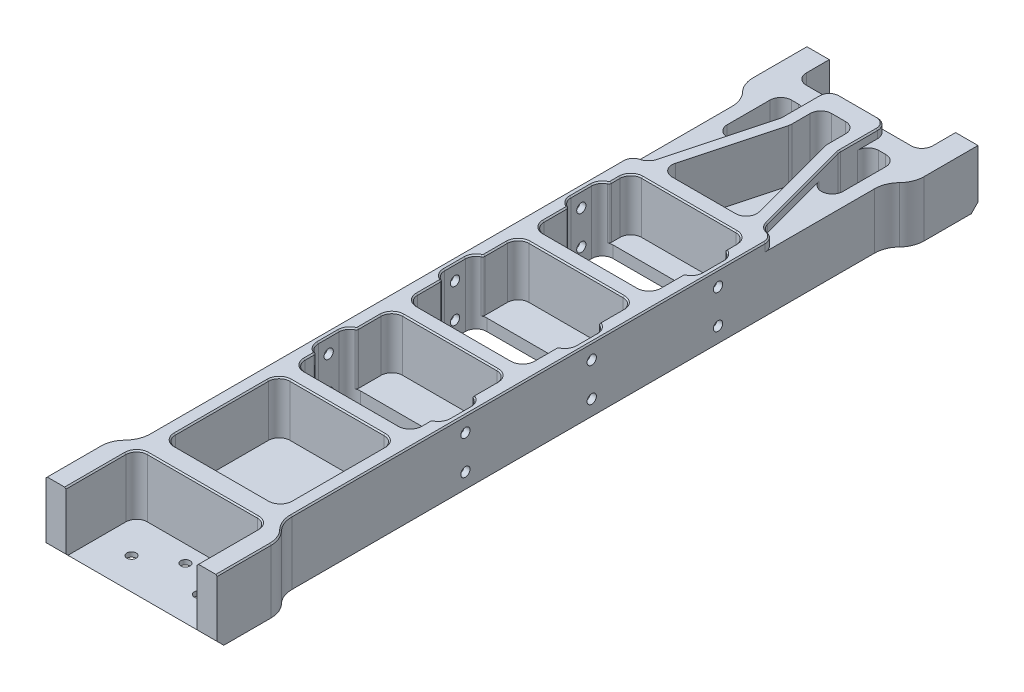
SolidWorks part; units mm, degrees
note: '?' marks a value the reader was unsure of.
material "Delrin 150"
ref_plane "Front Plane" through (0, 0, 0) normal (0, 0, 1) x (1, 0, 0)
ref_plane "Top Plane" through (0, 0, 0) normal (0, 1, 0) x (1, 0, 0)
ref_plane "Right Plane" through (0, 0, 0) normal (1, 0, 0) x (0, 0, -1)
ref_axis "Axis1" through (0, 0, -88.99) along (0, 0, 1)?
ref_axis "Axis2" through (0, -55, 0) along (0, 1, 0)?
ref_axis "Axis3" through (-88.99, 0, 0) along (1, 0, 0)?
sketch "Sketch1" plane through (0, 0, 0) normal (0, 0, 1) x (1, 0, 0)
  line L0 (-34.3291, 38.1) -> (-34.3291, 7)
  line L1 (-42.3291, 0) -> (42.3291, 0)
  line L2 (42.3291, 0) -> (42.3291, 38.1)
  line L3 (42.3291, 38.1) -> (34.3291, 38.1)
  line L4 (34.3291, 38.1) -> (34.3291, 7)
  line L5 (34.3291, 7) -> (-34.3291, 7)
  line L6 (0, 0) -> (0, 7) construction
  line L7 (-42.3291, 38.1) -> (-34.3291, 38.1)
  line L8 (-42.3291, 0) -> (-42.3291, 38.1)
  dimension "D1" = 8
  dimension "D2" = 38.1
  dimension "D3" = 7
  dimension "D4" = 84.6582
extrude "Boss-Extrude1" add sketch "Sketch1" along normal mid plane 451.725 contours L8 L7 L0 L5 L4 L3 L2 L1
sketch "Sketch2" plane through (0, 7, 0) normal (0, 1, 0) x (1, 0, 0)
  line L0 (-34.3291, -225.8625) -> (-34.3291, 225.8625) construction
  line L1 (-34.3291, -171.8625) -> (34.3291, -171.8625)
  line L2 (-34.3291, -171.8625) -> (-34.3291, -183.8625)
  line L3 (-34.3291, -183.8625) -> (34.3291, -183.8625)
  line L4 (34.3291, -171.8625) -> (34.3291, -183.8625)
  line L5 (34.3291, -225.8625) -> (34.3291, 225.8625) construction
  line L6 (34.3291, -225.8625) -> (-34.3291, -225.8625) construction
  line L7 (34.3291, 225.8625) -> (-34.3291, 225.8625) construction
  line L8 (-34.3291, 205.8625) -> (34.3291, 205.8625)
  line L9 (-34.3291, 205.8625) -> (-34.3291, 193.8625)
  line L10 (-34.3291, 193.8625) -> (34.3291, 193.8625)
  line L11 (34.3291, 205.8625) -> (34.3291, 193.8625)
  dimension "D1" = 12
  dimension "D2" = 42
  dimension "D3" = 20
  dimension "D4" = 12
extrude "Boss-Extrude2" add sketch "Sketch2" along normal up to surface (31.1 mm away) contours L8 L11 L10 L9
sketch "Sketch7" plane through (0, 0, 0) normal (0, -1, 0) x (1, 0, 0)
  line L0 (42.3291, -172.9915) -> (42.3291, -225.8625)
  line L2 (42.3291, -225.8625) -> (50.7791, -225.8625)
  line L3 (50.7791, -225.8625) -> (50.7791, -193.8625)
  line L4 (42.3291, -172.9915) -> (42.3291, -225.8625)
  line L5 (0, 0) -> (0, -225.8625) construction
  line L6 (-42.3291, -225.8625) -> (42.3291, -225.8625) construction
  line L7 (-42.3291, -172.9915) -> (-42.3291, -225.8625)
  line L8 (-50.7791, -225.8625) -> (-50.7791, -193.8625)
  line L9 (-42.3291, -225.8625) -> (-50.7791, -225.8625)
  line L10 (42.3291, 0) -> (0, 0) construction
  line L11 (42.3291, 225.8625) -> (42.3291, -225.8625) construction
  line L12 (-42.3291, 225.8625) -> (-50.7791, 225.8625)
  line L13 (-50.7791, 225.8625) -> (-50.7791, 193.8625)
  line L14 (-42.3291, 172.9915) -> (-42.3291, 225.8625)
  line L15 (42.3291, 172.9915) -> (42.3291, 225.8625)
  line L16 (50.7791, 225.8625) -> (50.7791, 193.8625)
  line L17 (42.3291, 225.8625) -> (50.7791, 225.8625)
  line L18 (42.3291, 172.9915) -> (42.3291, 225.8625)
  arc A0 (50.7791, -193.8625) -> (46.5541, -183.427) centre (35.7791, -193.8625) ccw
  arc A1 (46.5541, -183.427) -> (42.3291, -172.9915) centre (57.3291, -172.9915) cw
  arc A2 (-46.5541, -183.427) -> (-42.3291, -172.9915) centre (-57.3291, -172.9915) ccw
  arc A3 (-50.7791, -193.8625) -> (-46.5541, -183.427) centre (-35.7791, -193.8625) cw
  arc A4 (-50.7791, 193.8625) -> (-46.5541, 183.427) centre (-35.7791, 193.8625) ccw
  arc A5 (-46.5541, 183.427) -> (-42.3291, 172.9915) centre (-57.3291, 172.9915) cw
  arc A6 (46.5541, 183.427) -> (42.3291, 172.9915) centre (57.3291, 172.9915) ccw
  arc A7 (50.7791, 193.8625) -> (46.5541, 183.427) centre (35.7791, 193.8625) cw
  line M8 (42.3291, -225.8625) -> (42.3291, 225.8625)
  line M10 (-42.3291, 225.8625) -> (-42.3291, -225.8625)
  dimension "D3" = 15
  dimension "D4" = 15
  dimension "D1" = 8.45
  dimension "D2" = 32
extrude "Boss-Extrude3" add sketch "Sketch7" against normal up to surface (38.1 mm away) contours A4 A5 L12 L13 M10 | A7 L16 L17 A6 M8 | A3 L8 L9 A2 M10 | A0 A1 L2 L3 M8 up to face at (0, 38.1, -11)
sketch "Sketch3" plane through (50.7791, 0, 0) normal (1, 0, 0) x (0, 0, -1)
  line L0 (30, 38.1) -> (155.2069, 25.0682)
  line L1 (-172.9915, 38.1) -> (172.9915, 38.1) construction
  line L2 (156.5216, 25) -> (225.8625, 25)
  line L3 (225.8625, 0) -> (225.8625, 38.1) construction
  line L4 (30, 38.1) -> (225.8625, 38.1)
  line L5 (225.8625, 38.1) -> (225.8625, 25)
  line L6 (0, 0) -> (0, 38.1) construction
  line L7 (-172.9915, 0) -> (172.9915, 0) construction
  arc A0 (155.2069, 25.0682) -> (156.5216, 25) centre (156.5216, 37.7) ccw
  point P15 (155.8625, 25)
  dimension "D4" = 12.7
  dimension "D1" = 25
  dimension "D2" = 30
  dimension "D3" = 70
extrude "Cut-Extrude1" [suppressed] cut sketch "Sketch3" against normal through all
fillet "Fillet2" [suppressed] radius 12.7
hole_wizard "M5 Clearance Hole1" positions "Sketch5" profile "Sketch4" hole size "M5" standard "ANSI Metric" end condition through all
sketch "Sketch5" plane through (0, 7, 0) normal (0, 1, 0) x (1, 0, 0)
  line L0 (0, 0) -> (0, 225.8625) construction
  line L1 (34.3291, 225.8625) -> (-34.3291, 225.8625) construction
  line L3 (-28, 213.8625) -> (0, 213.8625) construction
  line L4 (0, -225.8625) -> (0, -183.8625) construction
  line L5 (34.3291, -225.8625) -> (-34.3291, -225.8625) construction
  line L6 (-34.3291, -183.8625) -> (34.3291, -183.8625) construction
  point P0 (-28, 213.8625)
  point P2 (0, 213.8625)
  point P20 (28, 213.8625)
  point P22 (0, -193.8625)
  point P24 (-20, -205.8625)
  point P34 (20, -205.8625)
  dimension "D1" = 12
  dimension "D2" = 56
  dimension "D3" = 40
  dimension "D4" = 12
  dimension "D5" = 20
sketch "Sketch4" plane through (-28, 7, -213.8625) normal (1, 0, 0) x (0, 0, 1)
  line L0 (0, 0) -> (0, 7)
  line L1 (0, 7) -> (2.75, 7)
  line L2 (2.75, 7) -> (2.75, 0)
  line L5 (2.75, 0) -> (0, 0)
  line L11 (0, -6.35) -> (0, 107.95) construction
  dimension "Thru Hole Dia." = 5.5
  dimension "Thru Hole Depth" = 7
sketch "Sketch6" plane through (0, 38.1, 0) normal (0, 1, 0) x (1, 0, 0)
  line L0 (-39, -225.8625) -> (-39, -183.8625)
  line L1 (-50.7791, -225.8625) -> (-34.3291, -225.8625) construction
  line L2 (-39, -183.8625) -> (39, -183.8625)
  line L3 (0, -183.8625) -> (0, -225.8625) construction
  line L4 (34.3291, -225.8625) -> (-34.3291, -225.8625) construction
  line L5 (-39, -225.8625) -> (39, -225.8625)
  line L6 (50.7791, -225.8625) -> (34.3291, -225.8625) construction
  line L7 (39, -225.8625) -> (39, -183.8625)
  line L8 (-34.3291, -183.8625) -> (34.3291, -183.8625) construction
  line L9 (-34.3291, -183.8625) -> (34.3291, -183.8625) construction
  dimension "D1" = 78
extrude "Cut-Extrude2" cut sketch "Sketch6" against normal offset from surface (35.35 mm away) 2.75 contours L5 L7 L2 L0 up to face at (-28, 0, -211.1125)
hole_wizard "M5 Clearance Hole2" positions "Sketch9" profile "Sketch8" hole size "M5" standard "ANSI Metric" end condition through all
sketch "Sketch9" plane through (42.3291, 0, 0) normal (1, 0, 0) x (0, 0, -1)
  line L0 (5, 9) -> (5, 29.1) construction
  line L3 (5, 9) -> (5, 0) construction
  line L4 (-172.9915, 0) -> (172.9915, 0) construction
  line L6 (-172.9915, 38.1) -> (172.9915, 38.1) construction
  line L7 (0, 0) -> (0, 38.1) construction
  line L8 (-172.9915, 38.1) -> (172.9915, 38.1) construction
  point P0 (-70, 29.1)
  point P2 (-70, 9)
  point P4 (5, 29.1)
  point P6 (5, 9)
  point P22 (80, 9)
  point P23 (80, 29.1)
  dimension "D1" = 20.1
  dimension "D2" = 150
  dimension "D3" = 5
  dimension "D4" = 9
sketch "Sketch8" plane through (42.3291, 29.1, 70) normal (0, 1, 0) x (0, 0, -1)
  line L0 (0, 0) -> (0, 93.1082)
  line L1 (0, 93.1082) -> (2.75, 93.1082)
  line L2 (2.75, 93.1082) -> (2.75, 0)
  line L5 (2.75, 0) -> (0, 0)
  line L11 (0, -6.35) -> (0, 107.95) construction
  dimension "Thru Hole Dia." = 5.5
  dimension "Thru Hole Depth" = 93.1082
sketch "Sketch10" plane through (0, 38.1, 0) normal (0, 1, 0) x (1, 0, 0)
  line L1 (-32.4791, 92.5) -> (32.4791, 92.5)
  line L2 (-38.8291, 86.15) -> (-38.8291, 73.85)
  line L3 (-32.4791, 67.5) -> (32.4791, 67.5)
  line L4 (38.8291, 86.15) -> (38.8291, 73.85)
  line L7 (-32.4791, 17.5) -> (32.4791, 17.5)
  line L8 (-38.8291, 11.15) -> (-38.8291, -1.15)
  line L9 (-32.4791, -7.5) -> (32.4791, -7.5)
  line L10 (38.8291, 11.15) -> (38.8291, -1.15)
  line L11 (0, 3.1125) -> (0, 6.8875) construction
  line L12 (34.3291, 3.1125) -> (-34.3291, 3.1125) construction
  line L13 (-34.3291, 6.8875) -> (34.3291, 6.8875) construction
  line L14 (0, 5) -> (38.8291, 5) construction
  line L15 (0, 78.1125) -> (0, 81.8875) construction
  line L16 (34.3291, 78.1125) -> (-34.3291, 78.1125) construction
  line L17 (-34.3291, 81.8875) -> (34.3291, 81.8875) construction
  line L18 (0, 80) -> (38.8291, 80) construction
  line L19 (-38.8291, -76.15) -> (-38.8291, -63.85)
  line L20 (-32.4791, -57.5) -> (32.4791, -57.5)
  line L21 (38.8291, -76.15) -> (38.8291, -63.85)
  line L22 (-32.4791, -82.5) -> (32.4791, -82.5)
  line L23 (42.3291, -172.9915) -> (42.3291, 172.9915) construction
  line L24 (-42.3291, -172.9915) -> (-42.3291, 172.9915) construction
  arc A0 (32.4791, 17.5) -> (38.8291, 11.15) centre (32.4791, 11.15) cw
  arc A1 (32.4791, -7.5) -> (38.8291, -1.15) centre (32.4791, -1.15) ccw
  arc A2 (-38.8291, -1.15) -> (-32.4791, -7.5) centre (-32.4791, -1.15) ccw
  arc A3 (-32.4791, 17.5) -> (-38.8291, 11.15) centre (-32.4791, 11.15) ccw
  arc A4 (32.4791, 92.5) -> (38.8291, 86.15) centre (32.4791, 86.15) cw
  arc A5 (32.4791, 67.5) -> (38.8291, 73.85) centre (32.4791, 73.85) ccw
  arc A6 (-38.8291, 73.85) -> (-32.4791, 67.5) centre (-32.4791, 73.85) ccw
  arc A7 (-32.4791, 92.5) -> (-38.8291, 86.15) centre (-32.4791, 86.15) ccw
  arc A8 (-32.4791, -82.5) -> (-38.8291, -76.15) centre (-32.4791, -76.15) cw
  arc A9 (-38.8291, -63.85) -> (-32.4791, -57.5) centre (-32.4791, -63.85) cw
  arc A10 (32.4791, -57.5) -> (38.8291, -63.85) centre (32.4791, -63.85) cw
  arc A11 (32.4791, -82.5) -> (38.8291, -76.15) centre (32.4791, -76.15) ccw
  point P34 (38.8291, -7.5)
  point P39 (-38.8291, 17.5)
  point P42 (38.8291, 92.5)
  point P45 (38.8291, 67.5)
  point P50 (-38.8291, 92.5)
  dimension "D2" = 6.35
  dimension "D1" = 25
  dimension "D3" = 3.5
  dimension "D4" = 3.5
extrude "Cut-Extrude3" cut sketch "Sketch10" against normal through all contours L9 A1 L10 A0 L7 A3 L8 A2 | L3 A5 L4 A4 L1 A7 L2 A6 | L22 A11 L21 A10 L20 A9 L19 A8
sketch "Sketch11" plane through (0, 38.1, 0) normal (0, 1, 0) x (1, 0, 0)
  line L0 (-37.5, 225.8625) -> (-37.5, 205.8625)
  line L1 (-50.7791, 225.8625) -> (-34.3291, 225.8625) construction
  line L2 (34.3291, 205.8625) -> (-34.3291, 205.8625) construction
  line L3 (-37.5, 205.8625) -> (37.5, 205.8625)
  line L4 (34.3291, 205.8625) -> (-34.3291, 205.8625) construction
  line L5 (-37.5, 225.8625) -> (37.5, 225.8625)
  line L6 (50.7791, 225.8625) -> (34.3291, 225.8625) construction
  line L7 (0, 225.8625) -> (0, 0) construction
  line L8 (37.5, 225.8625) -> (37.5, 205.8625)
  dimension "D1" = 75
extrude "Cut-Extrude4" cut sketch "Sketch11" against normal up to surface (31.1 mm away) up to face at (-28, 7, -211.1125)
fillet "Fillet3" radius 1.5 12 edges at (-34.3291, 22.55, -92.2245) (-34.3291, 22.55, -67.7755) (-34.3291, 22.55, -17.2245) (-34.3291, 22.55, 7.2245) (-34.3291, 22.55, 57.7755) (-34.3291, 22.55, 82.2245) (34.3291, 22.55, 82.2245) (34.3291, 22.55, 57.7755) (34.3291, 22.55, 7.2245) (34.3291, 22.55, -17.2245) (34.3291, 22.55, -67.7755) (34.3291, 22.55, -92.2245)
sketch "Sketch12" plane through (0, 38.1, 0) normal (0, 1, 0) x (1, 0, 0)
  line L0 (-34.3291, 18.2493) -> (-34.3291, 66.7507) construction
  line L1 (-34.3291, 47) -> (34.3291, 47)
  line L2 (-34.3291, 47) -> (-34.3291, 38)
  line L3 (-34.3291, 38) -> (34.3291, 38)
  line L4 (34.3291, 47) -> (34.3291, 38)
  line L5 (34.3291, 18.2493) -> (34.3291, 66.7507) construction
  line L6 (-34.3291, -56.7507) -> (-34.3291, -8.2493) construction
  line L7 (-34.3291, -28) -> (34.3291, -28)
  line L8 (-34.3291, -28) -> (-34.3291, -37)
  line L9 (-34.3291, -37) -> (34.3291, -37)
  line L10 (34.3291, -28) -> (34.3291, -37)
  line L11 (34.3291, -56.7507) -> (34.3291, -8.2493) construction
  line L12 (-38.8291, 5) -> (38.8291, 5) construction
  line L14 (38.8291, 11.15) -> (38.8291, -1.15) construction
  line L15 (-34.3291, -32.5) -> (34.3291, -32.5) construction
  line L17 (-38.8291, 11.15) -> (-38.8291, -1.15) construction
  line L18 (34.3291, 93.2493) -> (34.3291, 193.8625) construction
  line L19 (34.3291, 113.8625) -> (-34.3291, 113.8625)
  line L20 (34.3291, 113.8625) -> (34.3291, 104.8625)
  line L21 (34.3291, 104.8625) -> (-34.3291, 104.8625)
  line L22 (-34.3291, 113.8625) -> (-34.3291, 104.8625)
  line L23 (0, 38) -> (0, -28) construction
  line L24 (0, 47) -> (0, 104.8625) construction
  line L25 (0, 113.8625) -> (0, 193.8625) construction
  line L26 (-34.3291, 193.8625) -> (34.3291, 193.8625) construction
  line L27 (34.3291, -103.8625) -> (34.3291, -94.8625)
  line L28 (34.3291, -103.8625) -> (-34.3291, -103.8625)
  line L29 (-34.3291, -103.8625) -> (-34.3291, -94.8625)
  line L30 (34.3291, -94.8625) -> (-34.3291, -94.8625)
  point P26 (-34.3291, 42.5)
  dimension "D1" = 9
  dimension "D2" = 80
extrude "Boss-Extrude4" add sketch "Sketch12" against normal up to surface (31.1 mm away) contours L4 L1 L2 L3 | L19 L22 L21 L20 | L27 L30 L29 L28 | L7 L10 L9 L8 up to face at (0, 7, -42.5)
sketch "Sketch16" plane through (0, 38.1, 0) normal (0, 1, 0) x (1, 0, 0)
  line L0 (37.5, 225.8625) -> (-37.5, 225.8625) construction
  line L1 (-17.5, 225.8625) -> (-10.5, 225.8625)
  line L2 (-17.5, 225.8625) -> (-17.5, 176.6696)
  line L3 (27.0822, 113.8625) -> (34.3291, 113.8625)
  line L4 (-10.5, 225.8625) -> (-10.5, 175.748)
  line L5 (-17.5, 193.8625) -> (17.5, 193.8625)
  line L6 (-28, 213.8625) -> (0, 213.8625) construction
  line L7 (0, 213.8625) -> (28, 213.8625) construction
  line L8 (0, 213.8625) -> (0, 225.8625) construction
  line L9 (34.3291, 113.8625) -> (17.5, 176.6696)
  line L10 (17.5, 225.8625) -> (17.5, 176.6696)
  line L11 (17.5, 225.8625) -> (10.5, 225.8625)
  line L12 (10.5, 225.8625) -> (10.5, 175.748)
  line L13 (-14, 213.8625) -> (-14, 225.8625) construction
  line L14 (-27.0822, 113.8625) -> (-10.5, 175.748)
  line L15 (34.3291, 113.8625) -> (-34.3291, 113.8625) construction
  line L16 (-34.3291, 113.8625) -> (-17.5, 176.6696)
  line L17 (-34.3291, 113.8625) -> (-34.3291, 193.8625) construction
  line L18 (-30.7056, 113.8625) -> (-17.5, 163.1466) construction
  line L19 (-27.0822, 113.8625) -> (-34.3291, 113.8625)
  line L20 (27.0822, 113.8625) -> (10.5, 175.748)
  line L21 (-34.3291, 193.8625) -> (34.3291, 193.8625) construction
  dimension "D1" = 7
  dimension "D2" = 7
  dimension "D3" = 15
extrude "Boss-Extrude6" add sketch "Sketch16" against normal up to surface (31.1 mm away) contours L19 L14 L4 L5 L2 L16 | L20 L3 L9 L10 L5 L12 up to face at (0, 7, 12.6668)
fillet "Fillet4" radius 6.35 28 edges at (-34.3291, 22.55, -47) (-34.3291, 22.55, -38) (34.3291, 22.55, -47) (34.3291, 22.55, -38) (34.3291, 22.55, 28) (34.3291, 22.55, 37) (-34.3291, 22.55, 28) (-34.3291, 22.55, 37) (34.3291, 22.55, 94.8625) (-34.3291, 22.55, 94.8625) (-34.3291, 22.55, 103.8625) (34.3291, 22.55, 103.8625) (-34.3291, 22.55, -104.8625) (34.3291, 22.55, -104.8625) (34.3291, 22.55, -113.8625) (34.3291, 22.55, -193.8625) (17.5, 22.55, -193.8625) (17.5, 22.55, -176.6696) (-17.5, 22.55, -176.6696) (-17.5, 22.55, -193.8625) (-34.3291, 22.55, -193.8625) (-10.5, 22.55, -193.8625) (-10.5, 22.55, -175.748) (10.5, 22.55, -175.748) (10.5, 22.55, -193.8625) (27.0822, 22.55, -113.8625) (-27.0822, 22.55, -113.8625) (-34.3291, 22.55, -113.8625)
sketch "Sketch17" plane through (0, 38.1, 0) normal (0, 1, 0) x (1, 0, 0)
  line L0 (-17.5, 205.8625) -> (-17.5, 177.5055)
  line L1 (-34.3291, 113.8625) -> (-42.3291, 113.8625)
  line L2 (0, 0) -> (0, 104.8625) construction
  line L3 (27.9791, 104.8625) -> (-27.9791, 104.8625) construction
  line L4 (-21.8455, 160.452) -> (-17.7164, 175.862) construction
  line L6 (-17.7164, 175.862) -> (-34.3291, 113.8625)
  line L7 (18.8067, 113.8625) -> (-18.8067, 113.8625) construction
  line L8 (34.3291, 113.8625) -> (42.3291, 113.8625)
  line L9 (17.7164, 175.862) -> (34.3291, 113.8625)
  line L10 (17.5, 205.8625) -> (17.5, 177.5055)
  line L11 (-17.5, 187.5125) -> (-17.5, 177.5055) construction
  line L24 (37.5, 205.8625) -> (-37.5, 205.8625)
  line L25 (37.5, 205.8625) -> (-37.5, 205.8625)
  line L33 (-37.5, 205.8625) -> (-37.5, 225.8625)
  line L34 (-37.5, 225.8625) -> (-50.7791, 225.8625)
  line L35 (-50.7791, 225.8625) -> (-50.7791, 193.8625)
  line L36 (-42.3291, 172.9915) -> (-42.3291, -172.9915)
  line L37 (-50.7791, -193.8625) -> (-50.7791, -225.8625)
  line L38 (-50.7791, -225.8625) -> (-39, -225.8625)
  line L39 (-39, -225.8625) -> (-39, -183.8625)
  line L40 (-39, -183.8625) -> (39, -183.8625)
  line L41 (39, -183.8625) -> (39, -225.8625)
  line L42 (39, -225.8625) -> (50.7791, -225.8625)
  line L43 (50.7791, -225.8625) -> (50.7791, -193.8625)
  line L44 (42.3291, -172.9915) -> (42.3291, 172.9915)
  line L45 (50.7791, 193.8625) -> (50.7791, 225.8625)
  line L46 (50.7791, 225.8625) -> (37.5, 225.8625)
  line L47 (37.5, 225.8625) -> (37.5, 205.8625)
  line L57 (-37.5, 205.8625) -> (-37.5, 225.8625)
  line L58 (-37.5, 225.8625) -> (-50.7791, 225.8625)
  line L59 (-50.7791, 225.8625) -> (-50.7791, 193.8625)
  line L60 (-42.3291, 172.9915) -> (-42.3291, -172.9915)
  line L61 (-50.7791, -193.8625) -> (-50.7791, -225.8625)
  line L62 (-50.7791, -225.8625) -> (-39, -225.8625)
  line L63 (-39, -225.8625) -> (-39, -183.8625)
  line L64 (-39, -183.8625) -> (39, -183.8625)
  line L65 (39, -183.8625) -> (39, -225.8625)
  line L66 (39, -225.8625) -> (50.7791, -225.8625)
  line L67 (50.7791, -225.8625) -> (50.7791, -193.8625)
  line L68 (42.3291, -172.9915) -> (42.3291, 172.9915)
  line L69 (50.7791, 193.8625) -> (50.7791, 225.8625)
  line L70 (50.7791, 225.8625) -> (37.5, 225.8625)
  line L71 (37.5, 225.8625) -> (37.5, 205.8625)
  arc A0 (-17.7164, 175.862) -> (-17.5, 177.5055) centre (-23.85, 177.5055) ccw construction
  arc A1 (-17.7164, 175.862) -> (-17.5, 177.5055) centre (-23.85, 177.5055) ccw
  arc A2 (17.7164, 175.862) -> (17.5, 177.5055) centre (23.85, 177.5055) cw
  arc A13 (-50.7791, 193.8625) -> (-46.5541, 183.427) centre (-35.7791, 193.8625) ccw
  arc A14 (-42.3291, 172.9915) -> (-46.5541, 183.427) centre (-57.3291, 172.9915) ccw
  arc A15 (-46.5541, -183.427) -> (-42.3291, -172.9915) centre (-57.3291, -172.9915) ccw
  arc A16 (-46.5541, -183.427) -> (-50.7791, -193.8625) centre (-35.7791, -193.8625) ccw
  arc A19 (50.7791, -193.8625) -> (46.5541, -183.427) centre (35.7791, -193.8625) ccw
  arc A20 (42.3291, -172.9915) -> (46.5541, -183.427) centre (57.3291, -172.9915) ccw
  arc A21 (46.5541, 183.427) -> (42.3291, 172.9915) centre (57.3291, 172.9915) ccw
  arc A22 (46.5541, 183.427) -> (50.7791, 193.8625) centre (35.7791, 193.8625) ccw
  arc A25 (-50.7791, 193.8625) -> (-46.5541, 183.427) centre (-35.7791, 193.8625) ccw
  arc A26 (-42.3291, 172.9915) -> (-46.5541, 183.427) centre (-57.3291, 172.9915) ccw
  arc A27 (-46.5541, -183.427) -> (-42.3291, -172.9915) centre (-57.3291, -172.9915) ccw
  arc A28 (-46.5541, -183.427) -> (-50.7791, -193.8625) centre (-35.7791, -193.8625) ccw
  arc A31 (50.7791, -193.8625) -> (46.5541, -183.427) centre (35.7791, -193.8625) ccw
  arc A32 (42.3291, -172.9915) -> (46.5541, -183.427) centre (57.3291, -172.9915) ccw
  arc A33 (46.5541, 183.427) -> (42.3291, 172.9915) centre (57.3291, 172.9915) ccw
  arc A34 (46.5541, 183.427) -> (50.7791, 193.8625) centre (35.7791, 193.8625) ccw
  dimension "D1" = 0
extrude "Cut-Extrude5" cut sketch "Sketch17" against normal blind 5
hole_wizard "Tap Drill for M5x0.8 Tap1" [suppressed] positions "Sketch14" profile "Sketch13" hole size "M5x0.8" standard "ANSI Metric"
sketch "Sketch14" plane through (0, 38.1, 0) normal (0, 1, 0) x (1, 0, 0)
  line L4 (0, 38) -> (0, 47) construction
  line L5 (-27.9791, 38) -> (27.9791, 38) construction
  line L6 (-27.9791, 47) -> (27.9791, 47) construction
  line L8 (0, 105.3625) -> (0, 114.3625) construction
  line L9 (27.9791, 105.3625) -> (-27.9791, 105.3625) construction
  line L10 (18.8067, 114.3625) -> (-18.8067, 114.3625) construction
  line L12 (-35, 109.8625) -> (0, 109.8625) construction
  line L14 (-35, 42.5) -> (0, 42.5) construction
  line L24 (0, 38) -> (0, -28) construction
  line L25 (-27.9791, -28) -> (27.9791, -28) construction
  line L27 (0, 5) -> (52.4469, 5) construction
  point P0 (-40, 183.8625)
  point P2 (40, 183.8625)
  point P4 (35, 109.8625)
  point P6 (-35, 109.8625)
  point P8 (35, 42.5)
  point P10 (-35, 42.5)
  point P90 (-35, -99.8625)
  point P91 (35, -99.8625)
  point P92 (35, -32.5)
  point P93 (-35, -32.5)
  point P95 (-35, -177.8625)
  point P105 (35, -177.8625)
  dimension "D1" = 74
  dimension "D2" = 80
  dimension "D3" = 70
  dimension "D4" = 78
  dimension "D5" = 70
sketch "Sketch13" plane through (-40, 38.1, -183.8625) normal (1, 0, 0) x (0, 0, 1)
  line L0 (0, 0) -> (0, 16.2618)
  line L1 (0, 16.2618) -> (2.1, 15)
  line L2 (2.1, 15) -> (2.1, 0)
  line L5 (2.1, 0) -> (0, 0)
  line L10 (0, 16.2618) -> (-2.1, 15) construction
  line L11 (0, -6.35) -> (0, 107.95) construction
  dimension "Hole Dia." = 4.2
  dimension "Hole Depth" = 15
  dimension "Drill Angle" = 118
fillet "Fillet5" radius 6.35 8 edges at (34.3291, 22.55, 171.8625) (-34.3291, 22.55, 171.8625) (-34.3291, 35.6, -113.8625) (34.3291, 35.6, -113.8625) (-37.5, 20.05, -205.8625) (37.5, 20.05, -205.8625) (39, 20.425, 183.8625) (-39, 20.425, 183.8625)
fillet "Fillet6" radius 6.35 4 edges at (17.5, 35.6, -205.8625) (-17.5, 35.6, -205.8625) (-42.3291, 35.6, -113.8625) (42.3291, 35.6, -113.8625)
chamfer "Chamfer1" distance 0.75 angle 45 94 edges at (50.7791, 38.1, 209.8625) (49.6828, 38.1, 188.2333) (43.4254, 38.1, 178.6207) (42.3291, 38.1, 32.5317) (0, 38.1, -205.8625) (-42.3291, 38.1, 32.5317) (-43.4254, 38.1, 178.6207) (-49.6828, 38.1, 188.2333) (-50.7791, 38.1, 209.8625) (-39, 38.1, 208.0375) (0, 38.1, 183.8625) (39, 38.1, 208.0375) (-34.3291, 38.1, 137.8625) (-32.4692, 38.1, 105.7224) (0, 38.1, 171.8625) (0, 38.1, 103.8625) (32.4692, 38.1, 105.7224) (34.3291, 38.1, 137.8625) (-34.3291, 38.1, 85.8809) (-32.4692, 38.1, 93.0026) (-34.5622, 38.1, 82.4462) (0, 38.1, 94.8625) (-37.8424, 38.1, 79.5496) (32.4692, 38.1, 93.0026) (-38.8291, 38.1, 70) (34.3291, 38.1, 85.8809) (-37.8424, 38.1, 60.4504) (34.5622, 38.1, 82.4462) (-34.5622, 38.1, 57.5538) (37.8424, 38.1, 79.5496) (-34.3291, 38.1, 50.0504) (38.8291, 38.1, 70) (-32.4692, 38.1, 38.8599) (37.8424, 38.1, 60.4504) (0, 38.1, 37) (34.5622, 38.1, 57.5538) (32.4692, 38.1, 38.8599) (34.3291, 38.1, 50.0504) (-34.3291, 38.1, 14.9496) (-32.4692, 38.1, 26.1401) (-34.5622, 38.1, 7.4462) (0, 38.1, 28) (-37.8424, 38.1, 4.5496) (32.4692, 38.1, 26.1401) (-38.8291, 38.1, -5) (34.3291, 38.1, 14.9496) (-37.8424, 38.1, -14.5496) (34.5622, 38.1, 7.4462) (-34.5622, 38.1, -17.4462) (37.8424, 38.1, 4.5496) (-34.3291, 38.1, -24.9496) (38.8291, 38.1, -5) (-32.4692, 38.1, -36.1401) (37.8424, 38.1, -14.5496) (0, 38.1, -38) (34.5622, 38.1, -17.4462) (32.4692, 38.1, -36.1401) (34.3291, 38.1, -24.9496) (-34.3291, 38.1, -60.0504) (-32.4692, 38.1, -48.8599) (-34.5622, 38.1, -67.5538) (0, 38.1, -47) (-37.8424, 38.1, -70.4504) (32.4692, 38.1, -48.8599) (-38.8291, 38.1, -80) (34.3291, 38.1, -60.0504) (-37.8424, 38.1, -89.5496) (34.5622, 38.1, -67.5538) (-34.5622, 38.1, -92.4462) (37.8424, 38.1, -70.4504) (-34.3291, 38.1, -95.8809) (38.8291, 38.1, -80) (-32.4692, 38.1, -103.0026) (37.8424, 38.1, -89.5496) (0, 38.1, -104.8625) (34.5622, 38.1, -92.4462) (32.4692, 38.1, -103.0026) (34.3291, 38.1, -95.8809) (-32.4692, 38.1, 170.0026) (32.4692, 38.1, 170.0026) (-17.5543, 38.1, -176.6767) (-34.7233, 38.1, -115.7106) (34.7233, 38.1, -115.7106) (17.5543, 38.1, -176.6767) (-25.3922, 38.1, -147.2155) (25.3922, 38.1, -147.2155) (-17.5, 38.1, -188.509) (17.5, 38.1, -188.509) (41.0067, 38.1, -111.807) (15.6401, 38.1, -204.0026) (-15.6401, 38.1, -204.0026) (-41.0067, 38.1, -111.807) (-37.1401, 38.1, 185.7224) (37.1401, 38.1, 185.7224)
chamfer "Chamfer2" distance 4 angle 45 2 edges at (0, 0, 225.8625) (0, 0, -225.8625)
